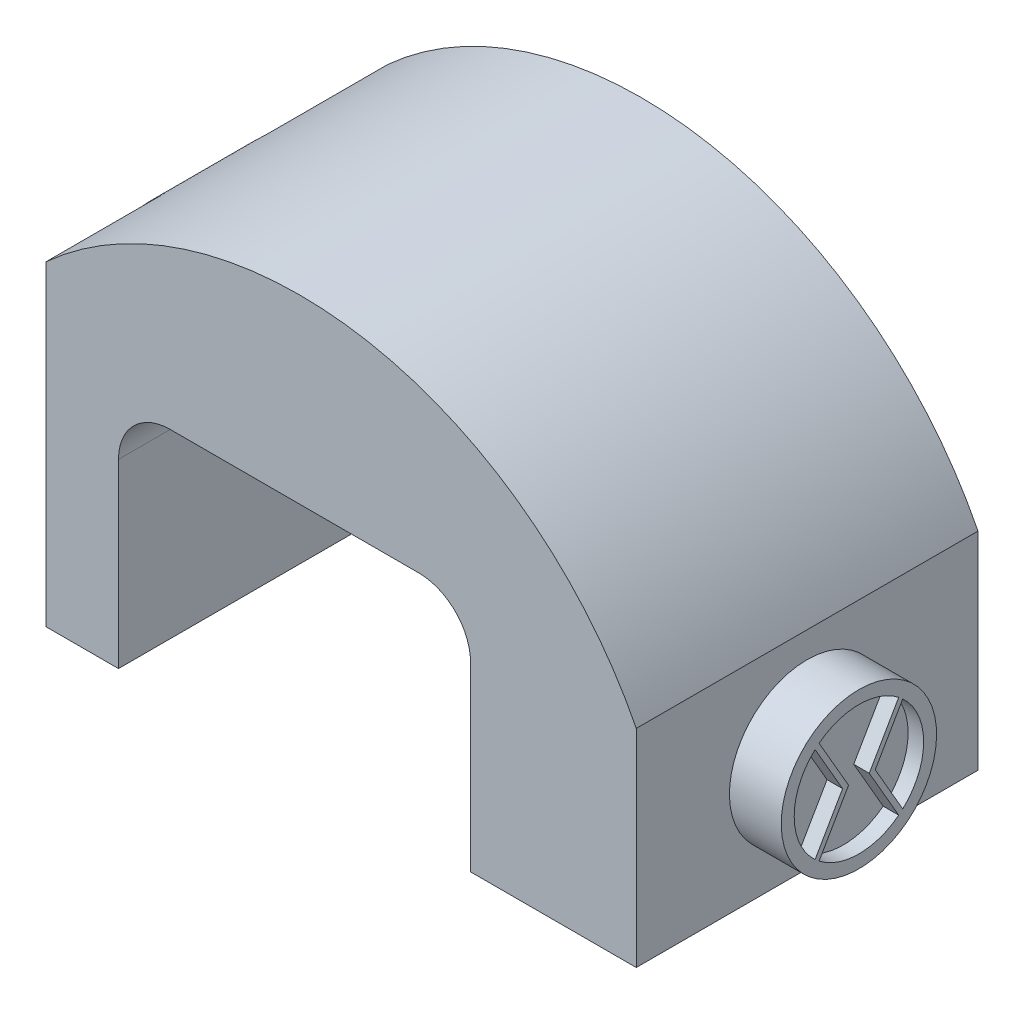
SolidWorks part; units mm, degrees
ref_plane "Front Plane" through (0, 0, 0) normal (0, 0, 1) x (1, 0, 0)
ref_plane "Top Plane" through (0, 0, 0) normal (0, 1, 0) x (1, 0, 0)
ref_plane "Right Plane" through (0, 0, 0) normal (1, 0, 0) x (0, 0, -1)
sketch "Sketch2" plane through (0, 0, 0) normal (0, 0, 1) x (1, 0, 0)
  line L1 (-65, 40) -> (65, 40)
  line L2 (-65, 40) -> (-65, -40)
  line L3 (-65, -40) -> (65, -40)
  line L4 (65, 40) -> (65, -40)
  line L5 (-65, 40) -> (65, -40) construction
  line L6 (-65, -40) -> (65, 40) construction
  arc A0 (-65, 0) -> (65, 0) centre (0, -32.8125) cw
  point P0 (0, 0)
  dimension "D1" = 130
  dimension "D2" = 80
extrude "Boss-Extrude1" add sketch "Sketch2" along normal blind 66 contours A0 L2 L3 L4 region at (0, -4.8075, 0)
sketch "Sketch4" plane through (65, 0, 0) normal (1, 0, 0) x (0, 0, -1)
  line L0 (-66, 0) -> (0, 0) construction
  line L2 (0, 0) -> (0, -40) construction
  circle A0 centre (-33, -20) radius 15
  dimension "D1" = 30
  dimension "D2" = 20
  dimension "D3" = 33
extrude "Boss-Extrude2" add sketch "Sketch4" along normal blind 10
sketch "Sketch3" plane through (0, 0, 66) normal (0, 0, 1) x (1, 0, 0)
  line L0 (-65, -40) -> (65, -40) construction
  line L1 (-25, 5) -> (23, 5)
  line L2 (-35, -5) -> (-35, -40)
  line L3 (-35, -40) -> (33, -40)
  line L4 (33, -5) -> (33, -40)
  line L5 (-65, 0) -> (-65, -40) construction
  line L6 (65, 0) -> (65, -40) construction
  arc A1 (23, 5) -> (33, -5) centre (23, -5) cw
  arc A2 (-35, -5) -> (-25, 5) centre (-25, -5) cw
  point P12 (33, 5)
  dimension "D2" = 32
  dimension "D4" = 10
  dimension "D1" = 30
  dimension "D3" = 45
extrude "Cut-Extrude2" cut sketch "Sketch3" against normal through all
sketch "Sketch5" plane through (0, -40, 0) normal (0, -1, 0) x (1, 0, 0)
  line L9 (-65, 66) -> (-49, 66)
  line L10 (-65, 66) -> (-65, 43)
  line L11 (-65, 43) -> (-49, 43)
  line L12 (-49, 66) -> (-49, 43)
  line L13 (-65, 0) -> (-49, 0)
  line L14 (-65, 0) -> (-65, 23)
  line L15 (-65, 23) -> (-49, 23)
  line L16 (-49, 0) -> (-49, 23)
  dimension "D1" = 16
  dimension "D2" = 16
  dimension "D3" = 23
  dimension "D4" = 23
extrude "Cut-Extrude3" cut sketch "Sketch5" against normal through all
sketch "Sketch6" plane through (0, -40, 0) normal (0, -1, 0) x (1, 0, 0)
  line L0 (-65, 43) -> (-65, 23) construction
  line L1 (-53.5, 38) -> (-43.5, 38)
  line L2 (-53.5, 38) -> (-53.5, 28)
  line L3 (-53.5, 28) -> (-43.5, 28)
  line L4 (-43.5, 38) -> (-43.5, 28)
  line L5 (-65, 43) -> (-49, 43) construction
  dimension "D1" = 10
  dimension "D2" = 10
  dimension "D3" = 11.5
  dimension "D4" = 5
extrude "Boss-Extrude3" add sketch "Sketch6" along normal blind 5
sketch "Sketch7" plane through (0, -40, 0) normal (0, -1, 0) x (1, 0, 0)
  line L0 (65, 66) -> (65, 0) construction
  line L1 (35.5, 19.9) -> (47.5, 19.9)
  line L2 (35.5, 19.9) -> (35.5, 7.9)
  line L3 (35.5, 7.9) -> (47.5, 7.9)
  line L4 (47.5, 19.9) -> (47.5, 7.9)
  line L5 (33, 0) -> (65, 0) construction
  line L7 (47.5, 19.9) -> (47.5, 46.1) construction
  line L9 (47.5, 46.1) -> (35.5, 46.1)
  line L10 (47.5, 46.1) -> (47.5, 58.1)
  line L11 (47.5, 58.1) -> (35.5, 58.1)
  line L12 (35.5, 46.1) -> (35.5, 58.1)
  dimension "D1" = 17.5
  dimension "D2" = 7.9
  dimension "D3" = 12
  dimension "D4" = 26.2
  dimension "D5" = 12
extrude "Boss-Extrude4" add sketch "Sketch7" along normal blind 5
sketch "Sketch8" plane through (75, 0, 0) normal (1, 0, 0) x (0, 0, -1)
  line L0 (-33, -7.5) -> (-33, -32.5) construction
  line L1 (-33, -20) -> (-35, -20) construction
  line L2 (-35, -20) -> (-33, -20) construction
  line L3 (-33, -20) -> (-31, -20) construction
  line L4 (-35, -20) -> (-45.5, -20) construction
  line L5 (-45.5, -20) -> (-20.5, -20) construction
  line L6 (-33, -20) -> (-32.8575, -20.1004)
  line L7 (-35, -20) -> (-40.6897, -10.1451)
  line L8 (-40.6897, -10.1451) -> (-35, -20)
  line L9 (-35, -20) -> (-40.6897, -29.8549)
  line L10 (-36.1547, -20) -> (-41.5557, -29.3549)
  line L11 (-36.1547, -20) -> (-41.5557, -10.6451)
  line L12 (-33.8453, -20) -> (-39.8237, -30.3549)
  line L13 (-33.8453, -20) -> (-39.8237, -9.6451)
  line L14 (-31, -20) -> (-20.5, -20) construction
  line L15 (-32.1547, -20) -> (-26.1763, -9.6451)
  line L16 (-32.1547, -20) -> (-26.1763, -30.3549)
  line L17 (-29.8453, -20) -> (-24.4443, -10.6451)
  line L18 (-29.8453, -20) -> (-24.4443, -29.3549)
  line L19 (-31, -20) -> (-25.3103, -29.8549)
  line L20 (-25.3103, -10.1451) -> (-31, -20)
  line L21 (-31, -20) -> (-25.3103, -10.1451)
  circle A0 centre (-33, -20) radius 12.5
  dimension "D1" = 25
  dimension "D3" = 2
  dimension "D4" = 60
  dimension "D5" = 60
  dimension "D6" = 1
  dimension "D7" = 1
extrude "Cut-Extrude4" cut sketch "Sketch8" against normal blind 3 contours L20 A0 L7 L9 L19 | L18 A0 L17 | L11 A0 L10 region at (75, -14.9258, 37.5907) region at (75, -20, 41.4417) region at (75, -20, 24.5583)
